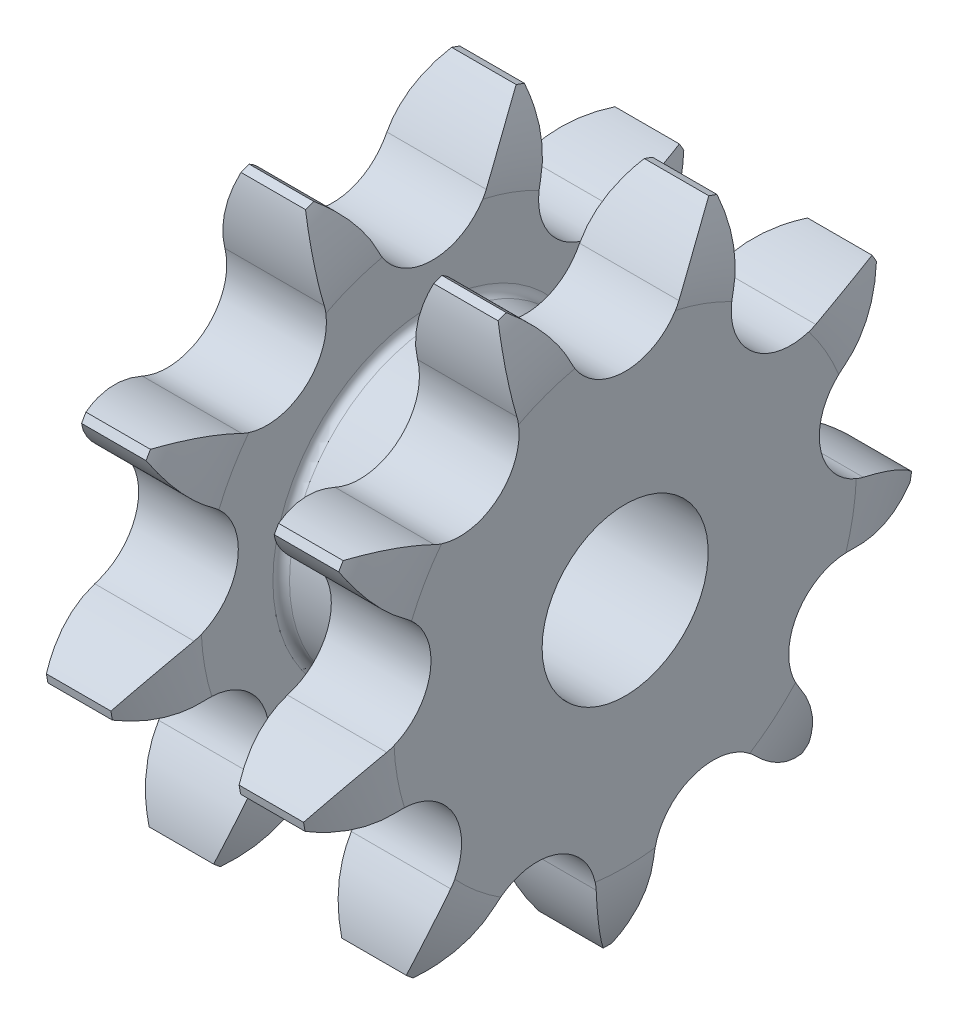
SolidWorks part; units mm, degrees
ref_plane "Plane1" through (0, 0, 0) normal (0, 0, 1) x (1, 0, 0)
ref_plane "Plane2" through (0, 0, 0) normal (0, 1, 0) x (1, 0, 0)
ref_plane "Plane3" through (0, 0, 0) normal (1, 0, 0) x (0, 0, -1)
sketch "Clipboard" plane through (0, 0, 0) normal (0, 1, 0) x (1, 0, 0)
  line L0 (0, 0) -> (12.5436, -1.9867)
  line L1 (-15, 0) -> (100, 0) construction
  line L2 (0, 0) -> (-0.8416, 0.9512)
  line L3 (0, 0) -> (-11.863, 4.5341)
  line L4 (0, 0) -> (3.0618, 0.4849)
  line L5 (0, 0) -> (-2.8109, -1.0484)
  line L6 (0, 0) -> (-17.5077, -11.8125)
  line L7 (-0.8416, 0.9512) -> (22.0505, 5.4009)
  line L8 (-76.2, 38.1) -> (-75.2, 38.1)
  line L9 (-73.4259, 41.6592) -> (-72.8306, 41.7344)
  line L10 (-73.4741, 12.7512) -> (-59.5541, 12.7512)
  circle A0 centre (0, 0) radius 4.255
  circle A1 centre (0, 0) radius 10.9305
  circle A2 centre (0, 0) radius 25
  dimension "Num_teeth" = 9
  dimension "Thickness" = 21.12
  dimension "Fillet_rad" = 0.6
sketch "BasProSke" plane through (0, 0, 0) normal (0, 1, 0) x (1, 0, 0)
  line L0 (-10, 0) -> (60, 0) construction
  line L1 (0, 0) -> (0, 16.7129)
  line L2 (0, 0) -> (21.12, 0)
  line L3 (21.12, 0) -> (21.12, 16.7129)
  line L4 (19.85, 22.2487) -> (1.27, 22.2487)
  arc A0 (0, 16.7129) -> (1.27, 22.2487) centre (12.7, 16.7129) cw
  arc A1 (21.12, 16.7129) -> (19.85, 22.2487) centre (8.42, 16.7129) ccw
  dimension "D1" = 12.7
  dimension "Thickness" = 21.12
  dimension "Diameter" = 44.4973
  dimension "G1" = 1.27
revolve "Base-Revolve" add sketch "BasProSke" angle 360 about L0
sketch "GrvSke" plane through (0, 0, 0) normal (0, 1, 0) x (1, 0, 0)
  line L0 (7.2, 16.7129) -> (7.2, 11.5305)
  line L1 (7.8, 10.9305) -> (13.32, 10.9305)
  line L2 (13.92, 11.5305) -> (13.92, 16.7129)
  line L3 (5.93, 22.2487) -> (15.19, 22.2487)
  line L4 (10.56, 0) -> (10.56, 52.07) construction
  line L5 (-10, 0) -> (60, 0) construction
  line L6 (0, 0) -> (35.56, 0) construction
  arc A0 (13.92, 16.7129) -> (15.19, 22.2487) centre (26.62, 16.7129) cw
  arc A1 (7.2, 16.7129) -> (5.93, 22.2487) centre (-5.5, 16.7129) ccw
  arc A2 (7.2, 11.5305) -> (7.8, 10.9305) centre (7.8, 11.5305) ccw
  arc A3 (13.32, 10.9305) -> (13.92, 11.5305) centre (13.32, 11.5305) ccw
  dimension "D1" = 12.7
  dimension "Diameter" = 44.4973
  dimension "Fillet_rad" = 0.6
  dimension "G1" = 1.27
  dimension "Grv_width" = 6.72
revolve "Groove" cut sketch "GrvSke" angle 360 about L6
sketch "TooCutSke" plane through (0, 0, 0) normal (1, 0, 0) x (0, 0, -1)
  line L0 (0, 18.6087) -> (3.8949, 16.7925) construction
  line L1 (0, 0) -> (0, 107) construction
  line L2 (0, 18.6087) -> (-10, 18.6087) construction
  line L3 (0, 18.6087) -> (-3.8949, 16.7925) construction
  arc A0 (3.8949, 16.7925) -> (7.8075, 21.3669) centre (14.0756, 12.0451) cw
  arc A1 (3.8949, 16.7925) -> (-3.8949, 16.7925) centre (0, 18.6087) cw
  arc A2 (-3.8949, 16.7925) -> (-7.8075, 21.3669) centre (-14.0756, 12.0451) ccw
  arc A3 (7.8075, 21.3669) -> (-7.8075, 21.3669) centre (0, 0) ccw
extrude "ToothCut" cut sketch "TooCutSke" along normal through all
pattern_circular "TeethCuts" count 9 every 40 about axis through (-10, 0, 0) along (1, 0, 0) of "ToothCut"
sketch "HubNeaOneSke" plane through (0, 0, 0) normal (-1, 0, 0) x (0, 0, 1)
  circle A0 centre (0, 0) radius 10.9305
  dimension "Diameter" = 21.861
extrude "HubNearOne" [suppressed] add sketch "HubNeaOneSke" along normal blind 2.2005
fillet "HubNearOneFillet" [suppressed] radius 0.6
sketch "HubNeaBotSke" plane through (0, 0, 0) normal (-1, 0, 0) x (0, 0, 1)
  circle A0 centre (0, 0) radius 10.9305
  dimension "Diameter" = 21.861
extrude "HubNearBoth" [suppressed] add sketch "HubNeaBotSke" along normal blind 1.1003
fillet "HubNearBothFillet" [suppressed] radius 0.6
ref_plane "FarPln" through (21.12, 0, 0) normal (1, 0, 0) x (0, 0, -1)
sketch "HubFarSke" plane through (21.12, 0, 0) normal (1, 0, 0) x (0, 0, -1)
  circle A0 centre (0, 0) radius 10.9305
  dimension "Diameter" = 21.861
extrude "HubFar" [suppressed] add sketch "HubFarSke" along normal blind 1.1003
fillet "HubFarFillet" [suppressed] radius 0.6
sketch "BorSke" plane through (0, 0, 0) normal (1, 0, 0) x (0, 0, -1)
  circle A0 centre (0, 0) radius 6
  dimension "Diameter" = 12
extrude "Bore" cut sketch "BorSke" along normal mid plane 46.641
sketch "KeySke" plane through (0, 0, 0) normal (1, 0, 0) x (0, 0, -1)
  line L0 (-1, 0) -> (-1, 7)
  line L1 (-1, 7) -> (1, 7)
  line L2 (1, 7) -> (1, 0)
  line L3 (0, 0) -> (0, 34) construction
  line L4 (-1, 0) -> (1, 0)
  dimension "Offset" = 7
  dimension "Width" = 2
extrude "Keyway" [suppressed] cut sketch "KeySke" along normal mid plane 46.641
pattern_circular "Keyway2" [suppressed] count 2 every 90 about axis through (-10, 0, 0) along (1, 0, 0) reverse direction yes
equation "' \"Pitch@Clipboard\" = 12.7"
equation "' \"Num_strands@Clipboard\" = 2"
equation "' \"Num_teeth@Clipboard\" = 9"
equation "' \"Hub_dia@Clipboard\" = 50"
equation "' \"Overall_len@Clipboard\" = 3"
equation "' \"Diameter@BorSke\" = 12"
equation "' \"T_dim@Clipboard\" = 1"
equation "' \"Width@KeySke\" = 2"
equation "' \"Dr@Clipboard\" = 8.51"
equation "' \"Face_width@Clipboard\" = 7.2"
equation "' \"Side_radius@Clipboard\" = 12.7"
equation "' \"Side_relief@Clipboard\" = 1.27"
equation "' \"Transv_pitch@Clipboard\" = 13.92"
equation "' \"Show_teeth@Clipboard\" = 9"
equation "' \"Fillet_rad@Clipboard\" = 0.6"
equation "' \"Plate_wid@Clipboard\" = 11.8"
equation "\"Num_teeth@Clipboard\" = int( \"Num_teeth@Clipboard\" )"
equation "\"Num_teeth@Clipboard\" = ((sgn( \"Num_teeth@Clipboard\" - 5.0)+1)*( \"Num_teeth@Clipboard\" - 5.0))/2 +5.0"
equation "\"Num_teeth@Clipboard\" = ((sgn( \"Num_teeth@Clipboard\" - 200.0)-1)*( \"Num_teeth@Clipboard\" - 200.0))/-2 +200.0"
equation "\"MHD@Clipboard\" = \"Pitch@Clipboard\" * (1.0 / tan(3.14159265 / \"Num_teeth@Clipboard\" )) - 1.04 * \"Plate_wid@Clipboard\" - 0.76"
equation "\"Thickness@Clipboard\"  = \"Face_width@Clipboard\" + (\"Num_strands@Clipboard\" - 1) * \"Transv_pitch@Clipboard\""
equation "\"OAL@Clipboard\" = \"Thickness@Clipboard\" + 2 * \"Fillet_rad@Clipboard\" + 1"
equation "\"MHD@Clipboard\" = ((sgn( \"MHD@Clipboard\" - \"Hub_dia@Clipboard\" )-1)*( \"MHD@Clipboard\" - \"Hub_dia@Clipboard\" ))/-2+ \"Hub_dia@Clipboard\""
equation "\"OAL@Clipboard\" = ((sgn( \"OAL@Clipboard\" - \"Overall_len@Clipboard\" )+1)*( \"OAL@Clipboard\" - \"Overall_len@Clipboard\" ))/2 + \"Overall_len@Clipboard\" + 0.0005"
equation "\"Num_teeth@TeethCuts\" = int( \"Show_teeth@Clipboard\" ) + 1"
equation "\"Num_teeth@TeethCuts\" = ((sgn( \"Num_teeth@TeethCuts\" - \"Num_teeth@Clipboard\" )-1)*( \"Num_teeth@TeethCuts\" - \"Num_teeth@Clipboard\" ))/-2+ \"Num_teeth@Clipboard\""
equation "\"Num_teeth@TeethCuts\" = ((sgn( \"Num_teeth@TeethCuts\" - 2.0)+1)*( \"Num_teeth@TeethCuts\" - 2.0))/2 +2.0"
equation "\"Angle@TeethCuts\" = 360.0 / \"Num_teeth@Clipboard\""
equation "\"Seat_radius@TooCutSke\" = ( \"Pitch@Clipboard\" / 2.0) / sin(3.14159265 / \"Num_teeth@Clipboard\" ) - \"Dr@Clipboard\" / 2.0 + \"Dr@Clipboard\" * 0.505"
equation "\"R1@TooCutSke\"  = \"Dr@Clipboard\" * 0.505"
equation "\"X@TooCutSke\" = 140.0 - (90.0 / \"Num_teeth@Clipboard\")"
equation "\"R2@TooCutSke\" = 0.12 * \"Dr@Clipboard\" * ( \"Num_teeth@Clipboard\" + 2.0)"
equation "\"Overcut@TooCutSke\" = 0.5 + 0.625 * \"Pitch@Clipboard\" - 0.5 * \"Dr@Clipboard\"  +  \"Pitch@Clipboard\" / 2.0 / sin(3.14159265 / \"Num_teeth@Clipboard\" )"
equation "\"Diameter@BasProSke\" = 2.0 * ( 0.625 * \"Pitch@Clipboard\" - 0.5 * \"Dr@Clipboard\"  +  \"Pitch@Clipboard\" / 2.0 / sin(3.14159265 / \"Num_teeth@Clipboard\" ))"
equation "\"Thickness@BasProSke\"  = \"Thickness@Clipboard\""
equation "\"G1@BasProSke\" =  \"Side_relief@Clipboard\""
equation "\"G2@BasProSke\" =  \"Side_relief@Clipboard\""
equation "\"D1@BasProSke\" =  \"Side_radius@Clipboard\""
equation "\"Diameter@GrvSke\" = \"Diameter@BasProSke\""
equation "\"G1@GrvSke\" = \"Side_relief@Clipboard\""
equation "\"D1@GrvSke\" = \"Side_radius@Clipboard\""
equation "\"Grv_diam@GrvSke\" =  \"Pitch@Clipboard\" * (1.0 / tan(3.14159265 / \"Num_teeth@Clipboard\" ))- 1.04 * \"Plate_wid@Clipboard\" - 0.76"
equation "\"Grv_width@GrvSke\" =  \"Transv_pitch@Clipboard\" - \"Face_width@Clipboard\""
equation "\"Offset@GrvSke\" = \"Grv_width@GrvSke\" / 2.0 + \"Face_width@Clipboard\""
equation "\"Fillet_rad@GrvSke\" = \"Fillet_rad@Clipboard\""
equation "\"Diameter@HubNeaOneSke\" = \"MHD@Clipboard\""
equation "\"Length@HubNearOne\" = \"OAL@Clipboard\" - \"Thickness@BasProSke\""
equation "\"Diameter@HubNeaBotSke\" = \"MHD@Clipboard\""
equation "\"Length@HubNearBoth\" = ( \"OAL@Clipboard\" - \"Thickness@BasProSke\" ) / 2.0"
equation "\"D1@HubNearOneFillet\" = \"Fillet_rad@Clipboard\""
equation "\"D1@HubNearBothFillet\" = \"Fillet_rad@Clipboard\""
equation "\"Thickness@FarPln\" = \"Thickness@BasProSke\""
equation "\"Diameter@HubFarSke\" = \"MHD@Clipboard\""
equation "\"Length@HubFar\" = ( \"OAL@Clipboard\" - \"Thickness@BasProSke\" ) / 2.0"
equation "\"D1@HubFarFillet\" = \"Fillet_rad@Clipboard\""
equation "\"D1@Bore\" = \"OAL@Clipboard\" * 2.0"
equation "\"D1@Keyway\" = \"OAL@Clipboard\" * 2.0"
equation "\"Offset@KeySke\" = \"T_dim@Clipboard\" + \"Diameter@BorSke\" / 2.0"
